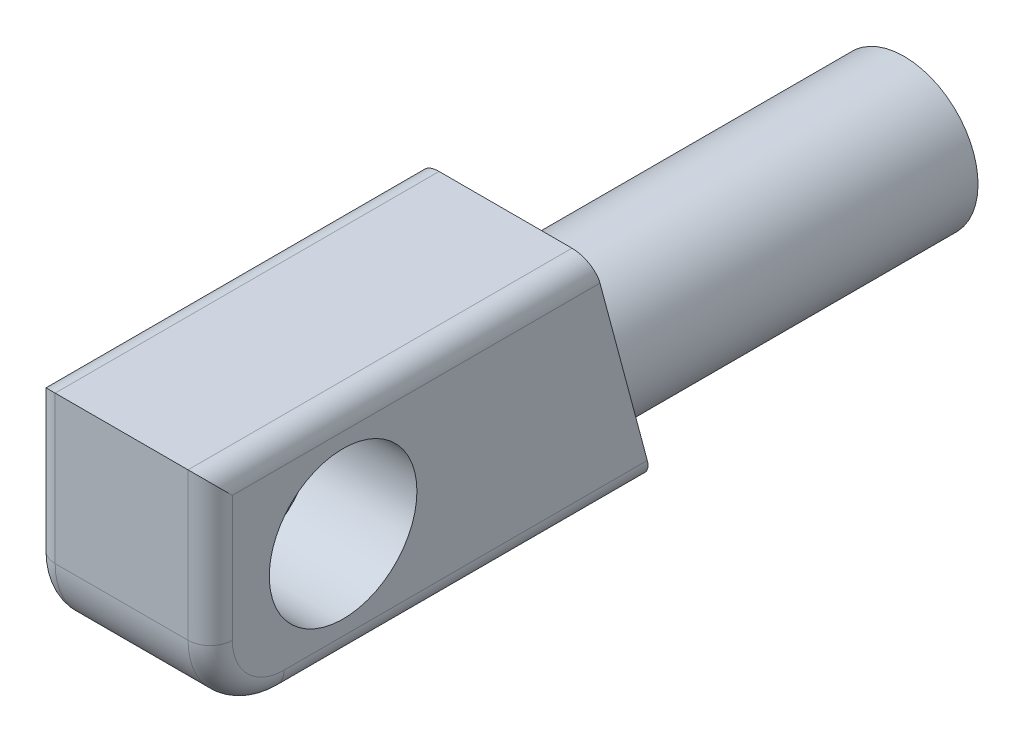
SolidWorks part; units mm, degrees
ref_plane "Front Plane" through (0, 0, 0) normal (0, 0, 1) x (1, 0, 0)
ref_plane "Top Plane" through (0, 0, 0) normal (0, 1, 0) x (1, 0, 0)
ref_plane "Right Plane" through (0, 0, 0) normal (1, 0, 0) x (0, 0, -1)
sketch "Sketch1" plane through (0, 0, 0) normal (1, 0, 0) x (0, 0, -1)
  line L0 (13, 7.5) -> (17, -7.5)
  line L1 (-13, -7.5) -> (13, -7.5) construction
  line L2 (-13, -7.5) -> (-13, 7.5) construction
  line L3 (-13, 7.5) -> (13, 7.5) construction
  line L4 (13, -7.5) -> (13, 7.5) construction
  line L5 (-13, -7.5) -> (13, 7.5) construction
  line L6 (-13, 7.5) -> (13, -7.5) construction
  line L7 (-13, -7.5) -> (17, -7.5)
  line L8 (-13, 7.5) -> (-13, -7.5)
  line L9 (-13, 7.5) -> (13, 7.5)
  point P0 (0, 0)
  dimension "D1" = 26
  dimension "D2" = 30
  dimension "D3" = 15
extrude "Boss-Extrude1" add sketch "Sketch1" along normal mid plane 12
sketch "Sketch2" plane through (0, 0, 0) normal (0, 0, 1) x (1, 0, 0)
  line L0 (0, 0) -> (0, -4.1844) construction
  line L1 (6, -7.5) -> (-6, -7.5) construction
  line L2 (-1, -6.5) -> (1, -6.5) construction
  line L3 (-1, -6.5) -> (-1, -7.5) construction
  line L4 (-1, -7.5) -> (1, -7.5)
  line L5 (1, -6.5) -> (1, -7.5) construction
  line L6 (-1, -6.5) -> (1, -7.5) construction
  line L7 (-1, -7.5) -> (1, -6.5) construction
  line L8 (-1, -7.5) -> (-1, -6.899)
  line L9 (1, -7.5) -> (1, -6.899)
  arc A0 (1, -6.899) -> (-1, -6.899) centre (0, -2) ccw
  circle A1 centre (0, -2) radius 4
  point P7 (0, -7)
  dimension "D1" = 10
  dimension "D2" = 8
  dimension "D3" = 2
  dimension "D4" = 2
extrude "Boss-Extrude2" add sketch "Sketch2" against normal blind 40 contours A0 A1 region at (-0.855, -7.1995, 0)
sketch "Sketch3" plane through (0, 0, 0) normal (1, 0, 0) x (0, 0, -1)
  line L0 (-4.9143, 0) -> (0, 0) construction
  circle A0 centre (-4, 0) radius 5
  dimension "D1" = 10
  dimension "D2" = 4
extrude "Cut-Extrude1" cut sketch "Sketch3" along normal through all from offset 1 offset against normal yes
fillet "Fillet1" radius 5 1 edges at (0, -7.5, 13)
fillet "Fillet2" radius 1.5 8 edges at (6, 2.5, 13) (6, -6.0355, 11.5355) (-6, -7.5, -4.5) (-6, -6.0355, 11.5355) (6, -7.5, -4.5) (6, 7.5, 0) (-6, 7.5, 0) (-6, 2.5, 13)
